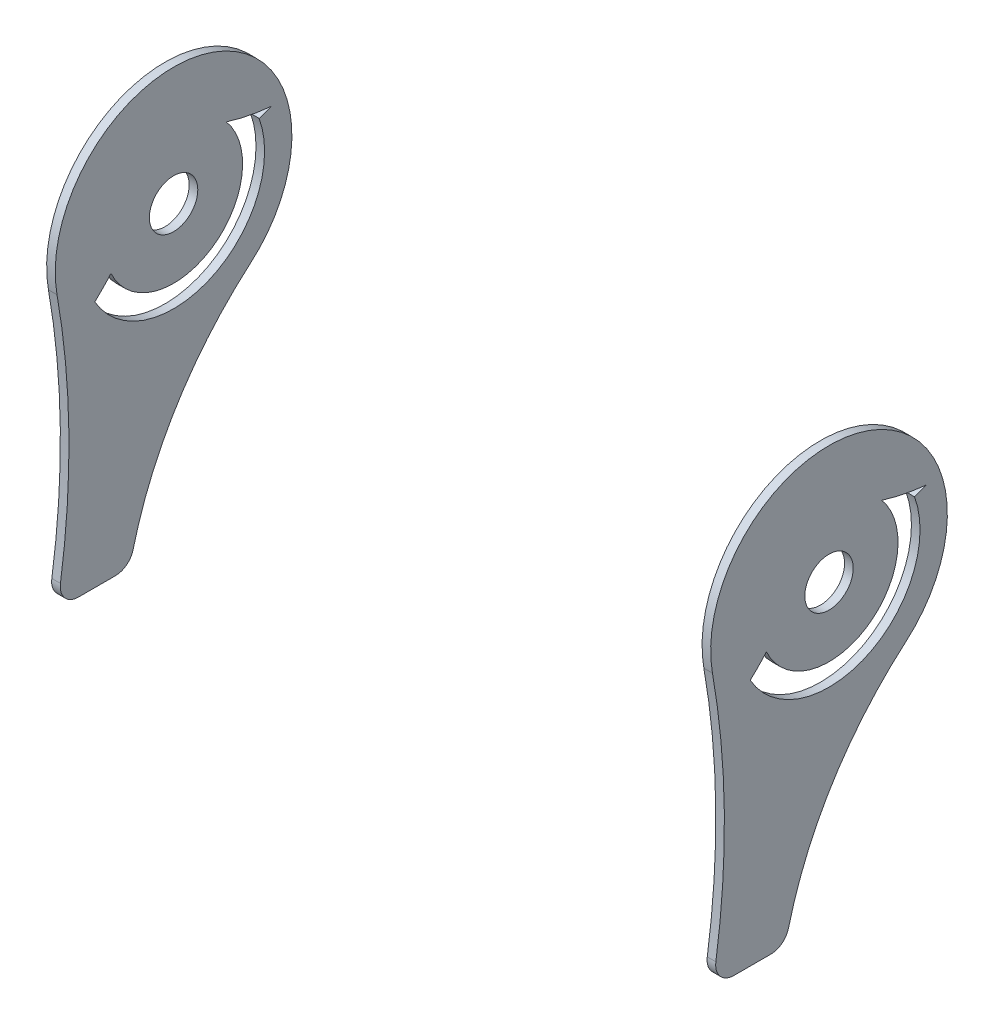
SolidWorks part; units mm, degrees
material "Ti-6Al-4VSolution treated and aged (SS)"
ref_plane "Front Plane" through (0, 0, 0) normal (0, 0, 1) x (1, 0, 0)
ref_plane "Top Plane" through (0, 0, 0) normal (0, 1, 0) x (1, 0, 0)
ref_plane "Right Plane" through (0, 0, 0) normal (1, 0, 0) x (0, 0, -1)
sketch "Sketch1" plane through (56.4, 0, 0) normal (1, 0, 0) x (0, 0, -1)
  line L0 (-176.22, -24.13) -> (-163.52, -24.13)
  line L1 (-176.22, -24.13) -> (-112.7785, -35.3164) construction
  arc A0 (-142.4774, 11.3114) -> (-176.2234, 23.4009) centre (-155.9, 26.9875) ccw
  arc A1 (-174.1784, 36.5691) -> (-176.2234, 23.4009) centre (-155.9, 26.9875) ccw construction
  circle A2 centre (-155.9, 26.9875) radius 4.2228
  arc A3 (-176.2234, 23.4009) -> (-176.22, -24.13) centre (-310.9451, -0.3743) cw
  arc A4 (-176.22, -24.13) -> (-176.2234, 23.4009) centre (-310.9451, -0.3743) ccw construction
  arc A5 (-163.52, -24.13) -> (-142.4774, 11.3114) centre (-100.7344, -37.4401) cw
  dimension "D1" = 8.4455
extrude "Boss-Extrude1" add sketch "Sketch1" along normal blind 1.5
sketch "Sketch2" plane through (57.9, 0, 0) normal (1, 0, 0) x (0, 0, -1)
  line L0 (-162.0897, 43.9936) -> (-161.3296, 41.9051)
  line L1 (-138.8939, 33.1772) -> (-140.9824, 32.4171)
  line L4 (-155.9, 26.9875) -> (-155.9, 53.9132) construction
  arc A0 (-166.8176, 21.9216) -> (-158.2659, 38.7884) centre (-155.9, 26.9875) ccw
  arc A1 (-161.3296, 41.9051) -> (-140.9824, 32.4171) centre (-155.9, 26.9875) ccw
  arc A2 (-142.4774, 11.3114) -> (-176.2234, 23.4009) centre (-155.9, 26.9875) ccw construction
  arc A3 (-162.0897, 43.9936) -> (-138.8939, 33.1772) centre (-135.3255, 71.1097) ccw
  arc A4 (-157.6009, 42.7711) -> (-158.2659, 38.7884) centre (-195.4604, 47.0454) cw
  arc A5 (-156.8864, 42.8318) -> (-143.1285, 36.4164) centre (-155.9, 26.9875) cw construction
  arc A6 (-156.8864, 42.8318) -> (-143.1285, 36.4164) centre (-135.3255, 71.1097) ccw construction
  circle A7 centre (-155.9, 26.9875) radius 18.0975 construction
  circle A8 centre (-155.9, 26.9875) radius 6.2547 construction
  circle A9 centre (-155.9, 26.9875) radius 4.2228 construction
  arc A10 (-166.8176, 21.9216) -> (-169.6374, 19.0314) centre (-195.4604, 47.0454) cw
  dimension "D1" = 4.7625
  dimension "D2" = 2.54
  dimension "D3" = 2.54
  dimension "D5" = 38.1
  dimension "D6" = 38.1
  dimension "D7" = 2.032
  dimension "D4" = 20
extrude "Cut-Extrude1" cut sketch "Sketch2" against normal up to next and the other way through all contours A0 A10 A1 L1 A3 L0 A4 region at (57.9, 20.1684, 167.9116)
fillet "Fillet1" radius 3.175 2 edges at (57.15, -24.13, 163.52) (57.15, -24.13, 176.22)
mirror "Mirror2" about plane through (0, 0, 0) normal (1, 0, 0) of bodies 105 101
equation "\"weapon shaft threads\"= 5 / 16"
equation "\"D1@Sketch1\"=\"weapon shaft threads\" + .02in"
equation "\"D1@Boss-Extrude1\"=1.5mm"
